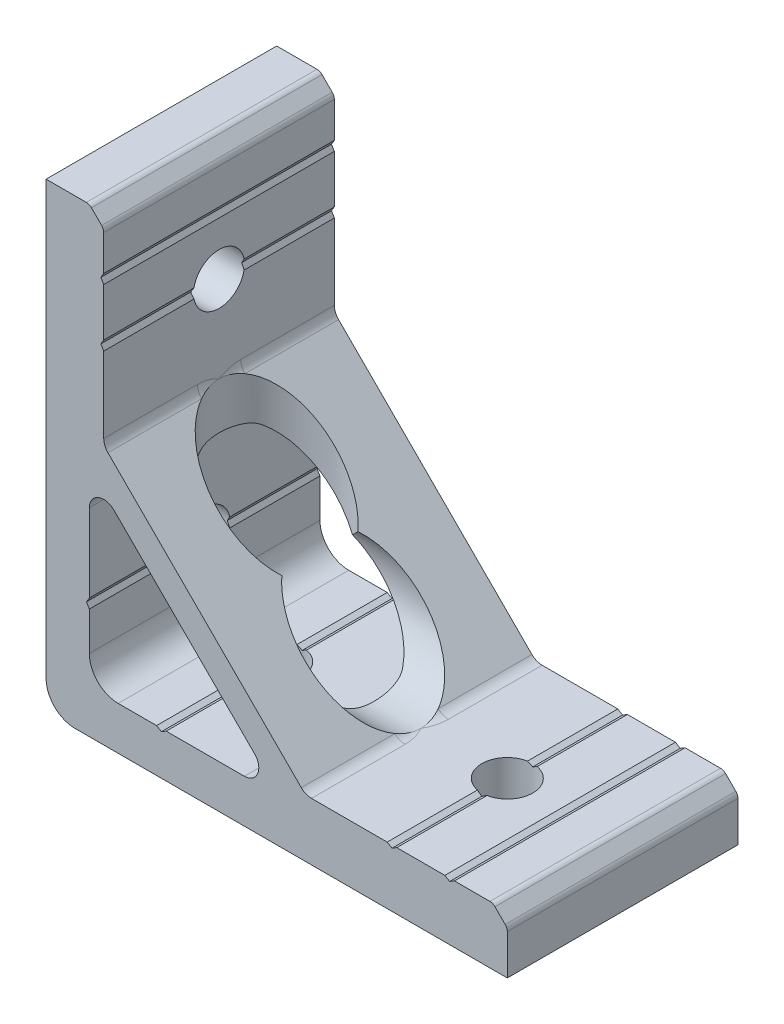
SolidWorks part; units mm, degrees
material "6063-T5"
ref_plane "Front Plane" through (0, 0, 0) normal (0, 0, 1) x (1, 0, 0)
ref_plane "Top Plane" through (0, 0, 0) normal (0, 1, 0) x (1, 0, 0)
ref_plane "Right Plane" through (0, 0, 0) normal (1, 0, 0) x (0, 0, -1)
ref_plane "Plane1" through (0, 0, 0) normal (0, 0, -1) x (-1, 0, 0)
sketch "Sketch1" plane through (0, 0, 0) normal (0, 0, -1) x (-1, 0, 0)
  line L0 (-4.7625, 50.8) -> (-50.8, 4.7625)
  line L1 (-50.8, 4.7625) -> (-50.8, 0)
  line L2 (-50.8, 0) -> (0, 0)
  line L3 (0, 0) -> (0, 50.8)
  line L4 (0, 50.8) -> (-4.7625, 50.8)
extrude "Boss-Extrude1" add sketch "Sketch1" against normal blind 25.4
sketch "Sketch2" plane through (0, 0, 25.4) normal (0, 0, 1) x (1, 0, 0)
  line L0 (6.35, 49.2125) -> (6.35, 44.9784)
  line L1 (6.35, 44.9784) -> (5.715, 43.9216)
  line L2 (5.715, 43.9216) -> (6.35, 43.9216)
  line L3 (6.35, 43.9216) -> (6.35, 38.6284)
  line L4 (6.35, 38.6284) -> (5.715, 38.6284)
  line L5 (5.715, 38.6284) -> (6.35, 37.5716)
  line L6 (6.35, 37.5716) -> (6.35, 28.575)
  line L7 (6.35, 28.575) -> (28.575, 6.35)
  line L8 (28.575, 6.35) -> (49.2125, 6.35)
  line L9 (49.2125, 6.35) -> (6.35, 49.2125)
extrude "Cut-Extrude1" cut sketch "Sketch2" against normal through all
sketch "Sketch3" plane through (0, 0, 25.4) normal (0, 0, 1) x (1, 0, 0)
  line L0 (38.6284, 6.35) -> (37.5716, 6.35)
  line L1 (37.5716, 6.35) -> (38.6284, 5.715)
  line L2 (38.6284, 5.715) -> (38.6284, 6.35)
extrude "Cut-Extrude2" cut sketch "Sketch3" against normal through all
sketch "Sketch4" plane through (0, 0, 25.4) normal (0, 0, 1) x (1, 0, 0)
  line L0 (44.9784, 6.35) -> (43.9216, 6.35)
  line L1 (43.9216, 6.35) -> (43.9216, 5.715)
  line L2 (43.9216, 5.715) -> (44.9784, 6.35)
extrude "Cut-Extrude3" cut sketch "Sketch4" against normal through all
sketch "Sketch5" plane through (0, 0, 25.4) normal (0, 0, 1) x (1, 0, 0)
  line L0 (13.2284, 4.7625) -> (21.8398, 4.7625)
  line L1 (22.9623, 7.4725) -> (7.4725, 22.9623)
  line L2 (4.7625, 21.8398) -> (4.7625, 13.2284)
  line L3 (4.7625, 13.2284) -> (4.1275, 13.2284)
  line L4 (4.1275, 13.2284) -> (4.7625, 12.1716)
  line L5 (4.7625, 12.1716) -> (4.7625, 4.7625)
  line L6 (4.7625, 4.7625) -> (12.1716, 4.7625)
  line L7 (12.1716, 4.7625) -> (12.1716, 4.1275)
  line L8 (12.1716, 4.1275) -> (13.2284, 4.7625)
  arc A0 (21.8398, 4.7625) -> (22.9623, 7.4725) centre (21.8398, 6.35) ccw
  arc A1 (7.4725, 22.9623) -> (4.7625, 21.8398) centre (6.35, 21.8398) ccw
extrude "Cut-Extrude4" cut sketch "Sketch5" against normal through all
draft "Draft1" type of draft neutral plane draft angle 59 faces to draft 1 face at (12.1716, 4.445, 12.7) neutral plane through (4.7625, 4.7625, 0) neutral plane normal (0, 1, 0) parameters "D1"=59
draft "Draft2" type of draft neutral plane draft angle 59 faces to draft 1 face at (4.445, 13.2284, 12.7) neutral plane through (4.7625, 21.8398, 0) neutral plane normal (1, 0, 0) parameters "D1"=59
draft "Draft3" type of draft neutral plane draft angle 59 faces to draft 2 face at (43.9216, 6.0325, 12.7) face at (38.6284, 6.0325, 12.7) neutral plane through (28.575, 6.35, 0) neutral plane normal (0, 1, 0) parameters "D1"=59
draft "Draft4" type of draft neutral plane draft angle 59 faces to draft 2 face at (6.0325, 43.9216, 12.7) face at (6.0325, 38.6284, 12.7) neutral plane through (6.35, 43.9216, 0) neutral plane normal (1, 0, 0) parameters "D1"=59
ref_plane "Plane2" through (0, 28.575, 0) normal (0, 1, 0) x (1, 0, 0)
hole_wizard "Hole1" positions "Sketch7" profile "Sketch6" legacy
sketch "Sketch7" plane through (0, 28.575, 0) normal (0, 1, 0) x (1, 0, 0)
  point P0 (12.7, -12.7)
sketch "Sketch6" plane through (12.7, 28.575, 12.7) normal (1, 0, 0) x (0, 0, 1)
  line L0 (0, 0) -> (0, 13.3576)
  line L1 (0, 13.3576) -> (6.35, 13.3576)
  line L2 (6.35, 13.3576) -> (6.35, 0)
  line L3 (6.35, 0) -> (0, 0)
  line L4 (0, 110) -> (0, -10) construction
  dimension "Diameter" = 12.7
  dimension "Depth" = 13.3576
hole_wizard "M5 Clearance Hole1" positions "Sketch9" profile "Sketch8" hole size "M5" standard "ANSI Metric"
sketch "Sketch9" plane through (0, 0, 0) normal (0, -1, 0) x (-1, 0, 0)
  point P0 (-38.1, -12.7)
sketch "Sketch8" plane through (38.1, 0, 12.7) normal (1, 0, 0) x (0, 0, -1)
  line L0 (0, 0) -> (0, 50.8)
  line L1 (0, 50.8) -> (2.8067, 50.8)
  line L2 (2.8067, 50.8) -> (2.8067, 0)
  line L5 (2.8067, 0) -> (0, 0)
  line L11 (0, -6.35) -> (0, 107.95) construction
  dimension "Thru Hole Dia." = 5.6134
  dimension "Thru Hole Depth" = 50.8
hole_wizard "M5 Clearance Hole2" positions "Sketch11" profile "Sketch10" hole size "M5" standard "ANSI Metric"
sketch "Sketch11" plane through (0, 0, 0) normal (0, -1, 0) x (-1, 0, 0)
  point P0 (-12.7, -12.7)
sketch "Sketch10" plane through (12.7, 0, 12.7) normal (1, 0, 0) x (0, 0, -1)
  line L0 (0, 0) -> (0, 50.8)
  line L1 (0, 50.8) -> (2.8067, 50.8)
  line L2 (2.8067, 50.8) -> (2.8067, 0)
  line L5 (2.8067, 0) -> (0, 0)
  line L11 (0, -6.35) -> (0, 107.95) construction
  dimension "Thru Hole Dia." = 5.6134
  dimension "Thru Hole Depth" = 50.8
hole_wizard "M5 Clearance Hole4" positions "Sketch15" profile "Sketch14" hole size "M5" standard "ANSI Metric"
sketch "Sketch15" plane through (0, 0, 0) normal (-1, 0, 0) x (0, 0, 1)
  point P0 (12.7, 38.1)
sketch "Sketch14" plane through (0, 38.1, 12.7) normal (0, 1, 0) x (0, 0, 1)
  line L0 (0, 0) -> (0, 50.8)
  line L1 (0, 50.8) -> (2.8067, 50.8)
  line L2 (2.8067, 50.8) -> (2.8067, 0)
  line L5 (2.8067, 0) -> (0, 0)
  line L11 (0, -6.35) -> (0, 107.95) construction
  dimension "Thru Hole Dia." = 5.6134
  dimension "Thru Hole Depth" = 50.8
hole_wizard "M5 Clearance Hole3" positions "Sketch13" profile "Sketch12" hole size "M5" standard "ANSI Metric"
sketch "Sketch13" plane through (0, 0, 0) normal (-1, 0, 0) x (0, 0, 1)
  point P0 (12.7, 12.7)
sketch "Sketch12" plane through (0, 12.7, 12.7) normal (0, 1, 0) x (0, 0, 1)
  line L0 (0, 0) -> (0, 50.8)
  line L1 (0, 50.8) -> (2.8067, 50.8)
  line L2 (2.8067, 50.8) -> (2.8067, 0)
  line L5 (2.8067, 0) -> (0, 0)
  line L11 (0, -6.35) -> (0, 107.95) construction
  dimension "Thru Hole Dia." = 5.6134
  dimension "Thru Hole Depth" = 50.8
ref_plane "Plane3" through (15.2174, 0, 0) normal (-1, 0, 0) x (0, 0, 1)
hole_wizard "Hole2" positions "Sketch17" profile "Sketch16" legacy
sketch "Sketch17" plane through (15.2174, 0, 0) normal (-1, 0, 0) x (0, 0, 1)
  point P0 (12.7, 12.7)
sketch "Sketch16" plane through (15.2174, 12.7, 12.7) normal (0, 1, 0) x (0, 0, 1)
  line L0 (0, 0) -> (0, 35.5826)
  line L1 (0, 35.5826) -> (6.35, 35.5826)
  line L2 (6.35, 35.5826) -> (6.35, 0)
  line L3 (6.35, 0) -> (0, 0)
  line L4 (0, 110) -> (0, -10) construction
  dimension "Diameter" = 12.7
  dimension "Depth" = 35.5826
fillet "Fillet1" radius 0.7938 4 edges at (50.8, 4.7625, 12.7) (6.35, 49.2125, 12.7) (4.7625, 50.8, 12.7) (49.2125, 6.35, 12.7) tangent propagation no
fillet "Fillet2" radius 1.5875 4 edges at (28.575, 6.35, 6.35) (28.575, 6.35, 19.05) (6.35, 28.575, 6.35) (6.35, 28.575, 19.05) tangent propagation no
fillet "Fillet3" radius 3.175 2 edges at (0, 0, 12.7) (4.7625, 4.7625, 12.7) tangent propagation no
